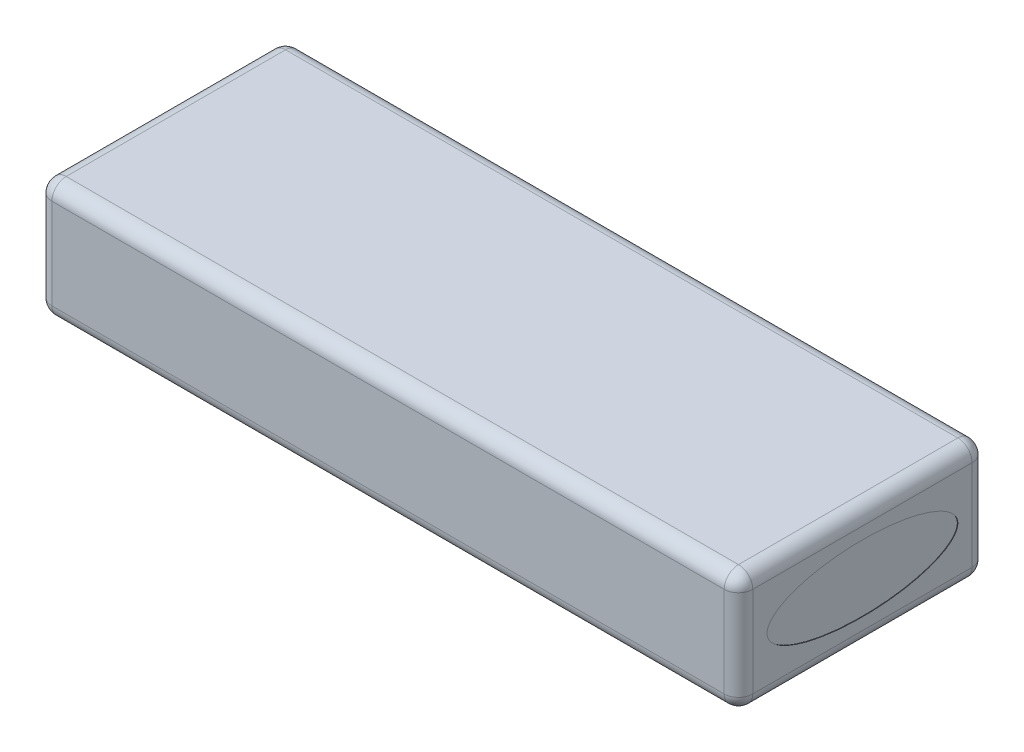
SolidWorks part; units mm, degrees
ref_plane "Plano frontal" through (0, 0, 0) normal (0, 0, 1) x (1, 0, 0)
ref_plane "Plano superior" through (0, 0, 0) normal (0, 1, 0) x (1, 0, 0)
ref_plane "Plano direito" through (0, 0, 0) normal (1, 0, 0) x (0, 0, -1)
sketch "Esboço1" plane through (0, 0, 0) normal (0, 1, 0) x (1, 0, 0)
  line L1 (-73.5, -26) -> (73.5, -26)
  line L2 (-73.5, -26) -> (-73.5, 26)
  line L3 (-73.5, 26) -> (73.5, 26)
  line L4 (73.5, -26) -> (73.5, 26)
  line L5 (-73.5, -26) -> (73.5, 26) construction
  line L6 (-73.5, 26) -> (73.5, -26) construction
  point P0 (0, 0)
  dimension "D1" = 147
  dimension "D2" = 52
extrude "Ressalto-extrusão1" add sketch "Esboço1" along normal blind 12.5 and the other way blind 12.5
fillet "Filete1" radius 3 4 edges at (0, -12.5, 26) (0, -12.5, -26) (0, 12.5, -26) (0, 12.5, 26)
fillet "Filete2" radius 3 16 edges at (-73.5, -11.6213, -25.1213) (-73.5, 0, -26) (-73.5, 11.6213, -25.1213) (-73.5, 12.5, 0) (-73.5, 11.6213, 25.1213) (-73.5, 0, 26) (-73.5, -11.6213, 25.1213) (-73.5, -12.5, 0) (73.5, -11.6213, -25.1213) (73.5, 11.6213, -25.1213) (73.5, 11.6213, 25.1213) (73.5, -11.6213, 25.1213) (73.5, 0, 26) (73.5, 12.5, 0) (73.5, 0, -26) (73.5, -12.5, 0)
sketch "Esboço2" plane through (73.5, 0, 0) normal (1, 0, 0) x (0, 0, -1)
  line L0 (0, 7) -> (0, -7) construction
  ellipse E0 centre (0, 0) end of major axis (20, 0) minor radius 7
  dimension "D1" = 14
  dimension "D2" = 40
extrude "Corte-extrusão1" cut sketch "Esboço2" against normal blind 0.1
sketch "Esboço3" plane through (-73.5, 0, 0) normal (-1, 0, 0) x (0, 0, 1)
  ellipse E0 centre (0, 0) end of major axis (-20, 0) minor radius 7 construction
  ellipse E1 centre (0, 0) end of major axis (-20, 0) minor radius 7
extrude "Corte-extrusão2" cut sketch "Esboço3" against normal blind 0.1
